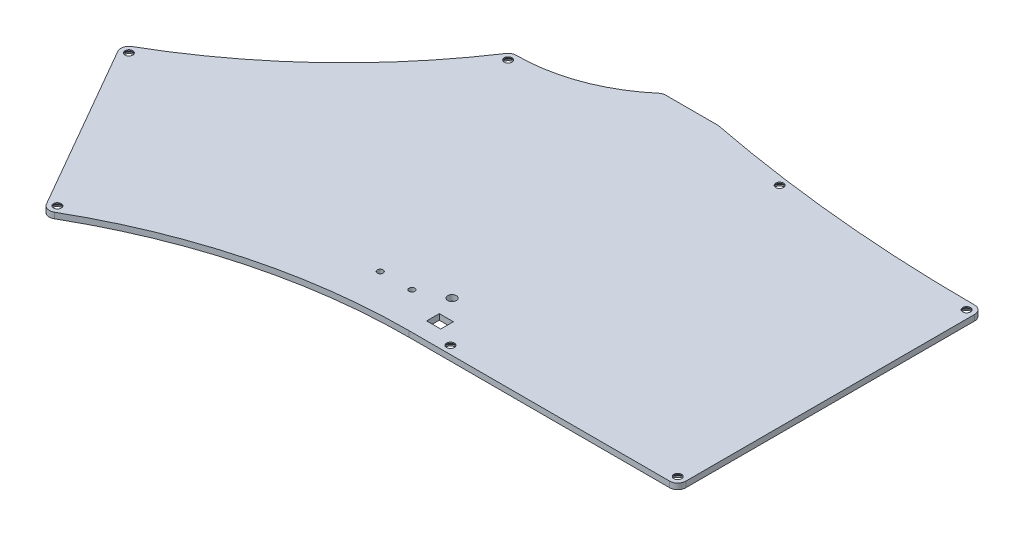
SolidWorks part; units mm, degrees
ref_plane "Front Plane" through (0, 0, 0) normal (0, 0, 1) x (1, 0, 0)
ref_plane "Top Plane" through (0, 0, 0) normal (0, 1, 0) x (1, 0, 0)
ref_plane "Right Plane" through (0, 0, 0) normal (1, 0, 0) x (0, 0, -1)
sketch "Main_line" plane through (0, 0, 0) normal (0, 1, 0) x (1, 0, 0)
  line L5 (53.2323, -110.3715) -> (58.1323, -110.3715) construction
  line L6 (53.2323, -110.3715) -> (53.2323, -114.7715) construction
  line L7 (53.2323, -114.7715) -> (58.1323, -114.7715) construction
  line L8 (58.1323, -110.3715) -> (58.1323, -114.7715) construction
  line L12 (53.5323, -110.5715) -> (57.8323, -110.5715) construction
  line L13 (57.9323, -110.6715) -> (57.9323, -114.4715) construction
  line L14 (53.4323, -114.4715) -> (53.4323, -110.6715) construction
  line L15 (57.8323, -114.5715) -> (53.5323, -114.5715) construction
  line L57 (53.0696, -120.9715) -> (143.7823, -120.9715)
  line L58 (-81.9059, -87.3079) -> (-48.2619, -145.8257)
  line L59 (44.7823, -4.9715) -> (26.7823, -4.9715)
  line L60 (146.7823, -117.9715) -> (146.7823, -17.4715)
  line L61 (53.0696, -120.9715) -> (143.7823, -120.9715) construction
  line L62 (-81.9059, -87.3079) -> (-48.2619, -145.8257) construction
  line L63 (44.7823, -4.9715) -> (26.7823, -4.9715) construction
  line L64 (146.7823, -117.9715) -> (146.7823, -17.4715) construction
  circle A0 centre (50.7823, -103.4715) radius 1.5 construction
  circle A1 centre (41.2823, -107.9515) radius 1 construction
  circle A2 centre (30.2823, -107.9515) radius 1 construction
  circle A3 centre (-79.3051, -85.8126) radius 1.35 construction
  circle A4 centre (-11.2177, -21.9715) radius 1.35 construction
  circle A5 centre (50.7823, -103.4715) radius 1.5 construction
  arc A121 (143.7823, -120.9715) -> (146.7823, -117.9715) centre (143.7823, -117.9715) ccw
  arc A122 (53.0696, -120.9715) -> (-44.1658, -146.9312) centre (53.0696, -316.055) ccw
  arc A123 (-48.2619, -145.8257) -> (-44.1658, -146.9312) centre (-45.6611, -144.3304) ccw
  arc A124 (-80.8004, -83.2119) -> (-81.9059, -87.3079) centre (-79.3051, -85.8126) ccw
  arc A125 (-80.8004, -83.2119) -> (-13.717, -20.312) centre (-180.7133, 90.5689) ccw
  arc A126 (-11.2177, -18.9715) -> (-13.717, -20.312) centre (-11.2177, -21.9715) ccw
  arc A127 (-11.2177, -18.9715) -> (24.8359, -5.6886) centre (-11.2177, 36.5999) ccw
  arc A128 (26.7823, -4.9715) -> (24.8359, -5.6886) centre (26.7823, -7.9715) ccw
  arc A129 (45.3528, -5.0262) -> (44.7823, -4.9715) centre (44.7823, -7.9715) ccw
  arc A130 (45.3528, -5.0262) -> (143.7823, -14.4715) centre (143.7823, 503.1206) ccw
  arc A131 (146.7823, -17.4715) -> (143.7823, -14.4715) centre (143.7823, -17.4715) ccw
  arc A132 (143.7823, -120.9715) -> (146.7823, -117.9715) centre (143.7823, -117.9715) ccw construction
  arc A133 (53.0696, -120.9715) -> (-44.1658, -146.9312) centre (53.0696, -316.055) ccw construction
  arc A134 (-48.2619, -145.8257) -> (-44.1658, -146.9312) centre (-45.6611, -144.3304) ccw construction
  circle A146 centre (143.7823, -117.9715) radius 1.35 construction
  circle A147 centre (143.7823, -117.9715) radius 1.35 construction
  circle A148 centre (64.7207, -117.9715) radius 1.35 construction
  circle A149 centre (-45.6611, -144.3304) radius 1.35 construction
  circle A150 centre (-79.3051, -85.8126) radius 1.35 construction
  circle A151 centre (-11.2177, -21.9715) radius 1.35 construction
  circle A152 centre (73.7823, -12.5168) radius 1.35 construction
  circle A153 centre (143.7823, -17.4715) radius 1.35 construction
  arc A154 (-80.8004, -83.2119) -> (-81.9059, -87.3079) centre (-79.3051, -85.8126) ccw construction
  arc A155 (-80.8004, -83.2119) -> (-13.717, -20.312) centre (-180.7133, 90.5689) ccw construction
  arc A156 (-11.2177, -18.9715) -> (-13.717, -20.312) centre (-11.2177, -21.9715) ccw construction
  arc A157 (-11.2177, -18.9715) -> (24.8359, -5.6886) centre (-11.2177, 36.5999) ccw construction
  arc A158 (26.7823, -4.9715) -> (24.8359, -5.6886) centre (26.7823, -7.9715) ccw construction
  arc A159 (45.3528, -5.0262) -> (44.7823, -4.9715) centre (44.7823, -7.9715) ccw construction
  arc A160 (45.3528, -5.0262) -> (143.7823, -14.4715) centre (143.7823, 503.1206) ccw construction
  arc A161 (146.7823, -17.4715) -> (143.7823, -14.4715) centre (143.7823, -17.4715) ccw construction
  dimension "D2" = 2
  dimension "D3" = 0.2
  dimension "D4" = 3
  dimension "D5" = 0.2
  dimension "D6" = 0.2
  dimension "D7" = 0.2
  dimension "D1" = 0
sketch "Sketch1" plane through (0, 0, 0) normal (0, 1, 0) x (1, 0, 0)
  line L33 (-81.7325, -87.2082) -> (-48.0885, -145.726)
  line L34 (53.0696, -120.7715) -> (143.7823, -120.7715)
  line L35 (146.5823, -117.9715) -> (146.5823, -17.4715)
  line L36 (44.7823, -5.1715) -> (26.7823, -5.1715)
  line L37 (-81.7325, -87.2082) -> (-48.0885, -145.726)
  line L38 (53.0696, -120.7715) -> (143.7823, -120.7715)
  line L39 (146.5823, -117.9715) -> (146.5823, -17.4715)
  line L40 (44.7823, -5.1715) -> (26.7823, -5.1715)
  circle A93 centre (143.7823, -17.4715) radius 1.35
  circle A94 centre (143.7823, -17.4715) radius 1.35 construction
  circle A95 centre (73.7823, -12.5168) radius 1.35
  circle A96 centre (-11.2177, -21.9715) radius 1.35
  circle A97 centre (-79.3051, -85.8126) radius 1.35
  circle A98 centre (-45.6611, -144.3304) radius 1.35
  circle A99 centre (64.7207, -117.9715) radius 1.35
  circle A100 centre (143.7823, -117.9715) radius 1.35
  arc A139 (-80.7007, -83.3852) -> (-81.7325, -87.2082) centre (-79.3051, -85.8126) ccw
  arc A140 (-48.0885, -145.726) -> (-44.2655, -146.7578) centre (-45.6611, -144.3304) ccw
  arc A141 (53.0696, -120.7715) -> (-44.2655, -146.7578) centre (53.0696, -316.055) ccw
  arc A142 (143.7823, -120.7715) -> (146.5823, -117.9715) centre (143.7823, -117.9715) ccw
  arc A143 (146.5823, -17.4715) -> (143.7823, -14.6715) centre (143.7823, -17.4715) ccw
  arc A144 (45.3147, -5.2226) -> (143.7823, -14.6715) centre (143.7823, 503.1206) ccw
  arc A145 (45.3147, -5.2226) -> (44.7823, -5.1715) centre (44.7823, -7.9715) ccw
  arc A146 (26.7823, -5.1715) -> (24.9657, -5.8408) centre (26.7823, -7.9715) ccw
  arc A147 (-11.2177, -19.1715) -> (24.9657, -5.8408) centre (-11.2177, 36.5999) ccw
  arc A148 (-11.2177, -19.1715) -> (-13.5504, -20.4227) centre (-11.2177, -21.9715) ccw
  arc A149 (-80.7007, -83.3852) -> (-13.5504, -20.4227) centre (-180.7133, 90.5689) ccw
  arc A150 (-80.7007, -83.3852) -> (-81.7325, -87.2082) centre (-79.3051, -85.8126) ccw
  arc A151 (-48.0885, -145.726) -> (-44.2655, -146.7578) centre (-45.6611, -144.3304) ccw
  arc A152 (53.0696, -120.7715) -> (-44.2655, -146.7578) centre (53.0696, -316.055) ccw
  arc A153 (143.7823, -120.7715) -> (146.5823, -117.9715) centre (143.7823, -117.9715) ccw
  arc A154 (146.5823, -17.4715) -> (143.7823, -14.6715) centre (143.7823, -17.4715) ccw
  arc A155 (45.3147, -5.2226) -> (143.7823, -14.6715) centre (143.7823, 503.1206) ccw
  arc A156 (45.3147, -5.2226) -> (44.7823, -5.1715) centre (44.7823, -7.9715) ccw
  arc A157 (26.7823, -5.1715) -> (24.9657, -5.8408) centre (26.7823, -7.9715) ccw
  arc A158 (-11.2177, -19.1715) -> (24.9657, -5.8408) centre (-11.2177, 36.5999) ccw
  arc A159 (-11.2177, -19.1715) -> (-13.5504, -20.4227) centre (-11.2177, -21.9715) ccw
  arc A160 (-80.7007, -83.3852) -> (-13.5504, -20.4227) centre (-180.7133, 90.5689) ccw
  dimension "D1" = 0.2
extrude "Main_plate" add sketch "Sketch1" along normal blind 2
sketch "Sketch2" plane through (0, 0, 0) normal (0, -1, 0) x (1, 0, 0)
  circle A0 centre (143.7823, 117.9715) radius 2.5
  circle A1 centre (64.7207, 117.9715) radius 2.5
  circle A2 centre (-45.6611, 144.3304) radius 2.5
  circle A3 centre (-79.3051, 85.8126) radius 2.5
  circle A4 centre (-11.2177, 21.9715) radius 2.5
  circle A5 centre (73.7823, 12.5168) radius 2.5
  circle A6 centre (143.7823, 17.4715) radius 2.5
  dimension "D1" = 5
extrude "Cut-Extrude1" cut sketch "Sketch2" against normal blind 1.7
chamfer "Chamfer1" distance 1.2 angle 45 7 edges at (143.7823, 1.7, 14.9715) (73.7823, 1.7, 10.0168) (-11.2177, 1.7, 19.4715) (-79.3051, 1.7, 83.3126) (-45.6611, 1.7, 141.8304) (64.7207, 1.7, 115.4715) (143.7823, 1.7, 115.4715)
sketch "Sketch3" plane through (0, 0, 0) normal (0, -1, 0) x (1, 0, 0)
  circle A0 centre (41.2823, 107.9515) radius 1
  circle A1 centre (30.2823, 107.9515) radius 1
  circle A2 centre (41.2823, 107.9515) radius 1 construction
extrude "Led_hole" cut sketch "Sketch3" against normal through all
sketch "Sketch4" plane through (0, 0, 0) normal (0, -1, 0) x (1, 0, 0)
  line L1 (53.2323, 114.7715) -> (58.1323, 114.7715)
  line L2 (53.2323, 114.7715) -> (53.2323, 110.3715)
  line L3 (53.2323, 110.3715) -> (58.1323, 110.3715)
  line L4 (58.1323, 114.7715) -> (58.1323, 110.3715)
extrude "Main_switch_hole" cut sketch "Sketch4" against normal through all
sketch "Sketch5" plane through (0, 0, 0) normal (0, -1, 0) x (1, 0, 0)
  circle A0 centre (50.7823, 103.4715) radius 1.5
  circle A1 centre (50.7823, 103.4715) radius 1.5 construction
extrude "Reset_hole" cut sketch "Sketch5" against normal through all
